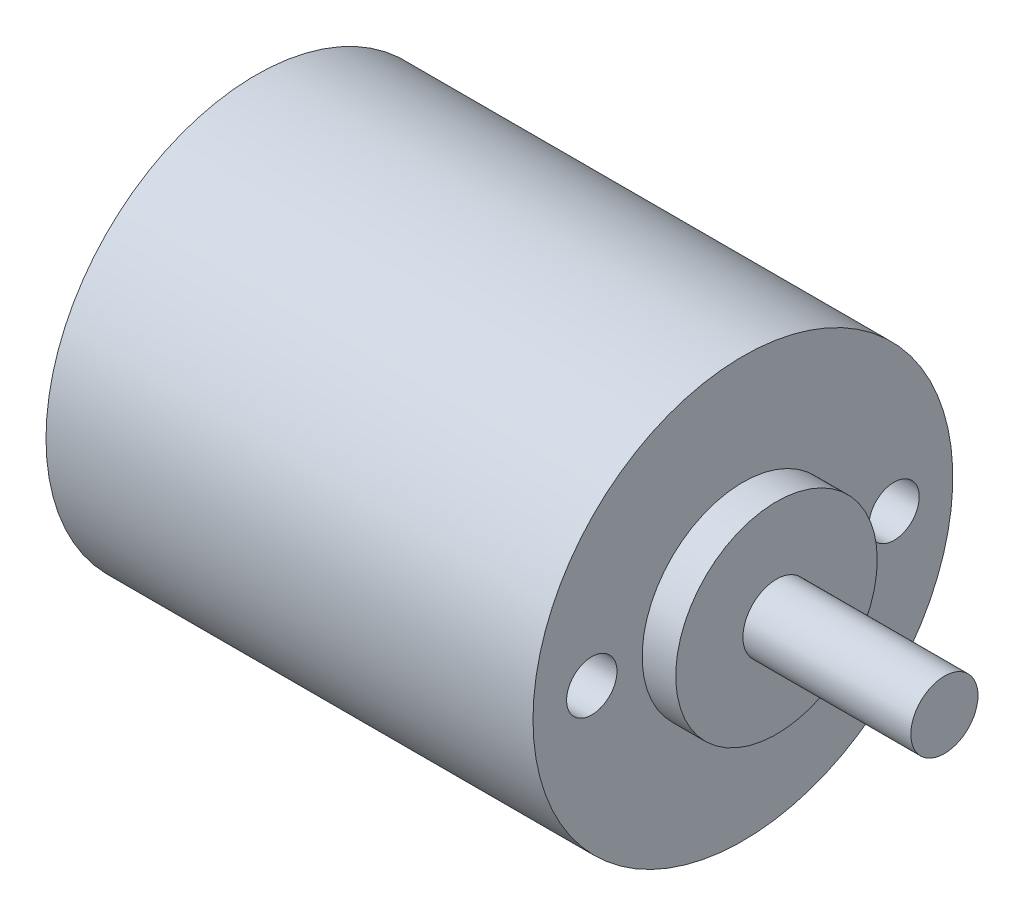
SolidWorks part; units mm, degrees
ref_plane "前视基准面" through (0, 0, 0) normal (0, 0, 1) x (1, 0, 0)
ref_plane "上视基准面" through (0, 0, 0) normal (0, 1, 0) x (1, 0, 0)
ref_plane "右视基准面" through (0, 0, 0) normal (1, 0, 0) x (0, 0, -1)
sketch "草图1" plane through (0, 0, 0) normal (1, 0, 0) x (0, 0, -1)
  circle A0 centre (0, 0) radius 12.5
  dimension "D1" = 25
extrude "凸台-拉伸3" add sketch "草图1" along normal blind 29
sketch "草图4" plane through (29, 0, 0) normal (1, 0, 0) x (0, 0, -1)
  circle A0 centre (0, 0) radius 6
  dimension "D1" = 12
extrude "凸台-拉伸4" add sketch "草图4" along normal blind 2
sketch "草图5" plane through (31, 0, 0) normal (1, 0, 0) x (0, 0, -1)
  circle A0 centre (0, 0) radius 2
  dimension "D1" = 4
extrude "凸台-拉伸5" add sketch "草图5" along normal blind 10
sketch "草图6" plane through (41, 0, 0) normal (1, 0, 0) x (0, 0, -1)
  circle A0 centre (0, 0) radius 9 construction
  circle A1 centre (-9, 0) radius 1.5
  circle A2 centre (9, 0) radius 1.5
  dimension "D1" = 18
  dimension "D2" = 3
  dimension "D3" = 3
extrude "切除-拉伸1" cut sketch "草图6" against normal blind 19
sketch "草图7" plane through (0, 0, 0) normal (-1, 0, 0) x (0, 0, 1)
  line L0 (0, 0) -> (0, -6) construction
  circle A0 centre (0, -6) radius 3.25
  dimension "D2" = 6.5
  dimension "D1" = 6
extrude "凸台-拉伸6" add sketch "草图7" along normal blind 5.5
